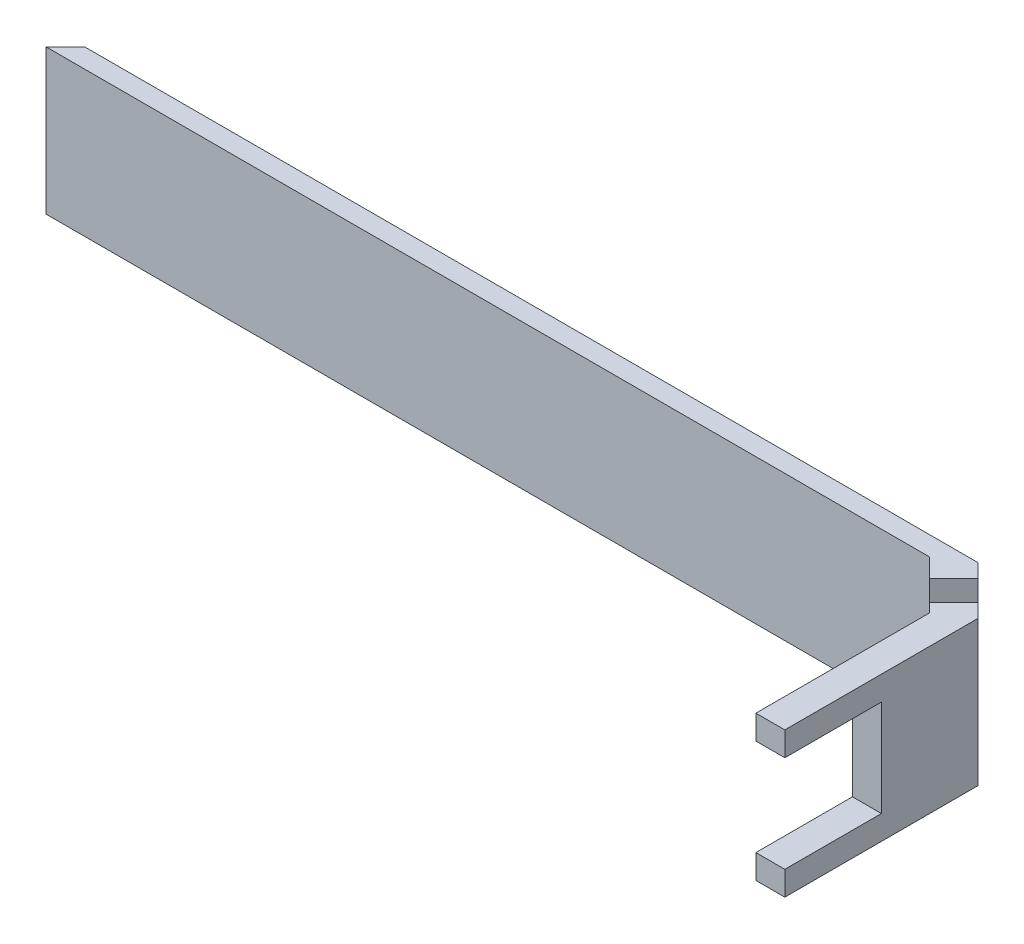
SolidWorks part; units mm, degrees
ref_plane "Front Plane" through (0, 0, 0) normal (0, 0, 1) x (1, 0, 0)
ref_plane "Top Plane" through (0, 0, 0) normal (0, 1, 0) x (1, 0, 0)
ref_plane "Right Plane" through (0, 0, 0) normal (1, 0, 0) x (0, 0, -1)
sketch "Sketch1" plane through (0, 0, 0) normal (0, 1, 0) x (1, 0, 0)
  line L0 (-48.5, 13.5) -> (51.5, 13.5)
  line L1 (51.5, 13.5) -> (51.5, -11.5)
  line L2 (51.5, -11.5) -> (48.5, -11.5)
  line L3 (48.5, -11.5) -> (48.5, 11.5)
  line L4 (48.5, 11.5) -> (-48.5, 11.5)
  line L5 (-48.5, 11.5) -> (-48.5, 13.5)
  point P2 (0, 11.5)
  point P7 (48.5, 0)
  dimension "D1" = 3
  dimension "D2" = 2
  dimension "D3" = 100
  dimension "D4" = 25
extrude "Boss-Extrude1" add sketch "Sketch1" along normal blind 15
chamfer "Chamfer1" distance 5 angle 45 2 edges at (48.5, 7.5, -11.5) (51.5, 7.5, -13.5)
sketch "Sketch3" plane through (51.5, 0, 0) normal (1, 0, 0) x (0, 0, -1)
  line L0 (-11.5, 15) -> (-11.5, 0) construction
  line L1 (-11.5, 12.5) -> (-1.5, 12.5)
  line L2 (-11.5, 12.5) -> (-11.5, 2.5)
  line L3 (-11.5, 2.5) -> (-1.5, 2.5)
  line L4 (-1.5, 12.5) -> (-1.5, 2.5)
  line L5 (8.5, 0) -> (8.5, 15) construction
  point P8 (8.5, 7.5)
  point P9 (-1.5, 7.5)
  dimension "D1" = 10
  dimension "D2" = 10
extrude "Cut-Extrude1" cut sketch "Sketch3" against normal blind 24
chamfer "Chamfer2" distance 2.5 angle 45 1 edges at (-48.5, 7.5, -13.5)
sketch "Sketch4" plane through (30, 0, -30) normal (0.7071, 0, -0.7071) x (-0.7071, 0, -0.7071)
  line L1 (-28.3701, 3) -> (-25.3701, 3)
  line L2 (-28.3701, 3) -> (-28.3701, 0)
  line L3 (-28.3701, 0) -> (-25.3701, 0)
  line L4 (-25.3701, 3) -> (-25.3701, 0)
  line L5 (-30.4056, 15) -> (-23.3345, 15) construction
  line L7 (-28.3701, 15) -> (-25.3701, 15)
  line L8 (-28.3701, 15) -> (-28.3701, 12)
  line L9 (-28.3701, 12) -> (-25.3701, 12)
  line L10 (-25.3701, 15) -> (-25.3701, 12)
  line L11 (-23.3345, 0) -> (-30.4056, 0) construction
  point P10 (-26.8701, 15)
  point P11 (-26.8701, 3)
  dimension "D1" = 3
  dimension "D2" = 3
  dimension "D4" = 3
extrude "Cut-Extrude2" cut sketch "Sketch4" against normal up to surface (3.5355 mm away) up to face at (46, 7.5, -9)
